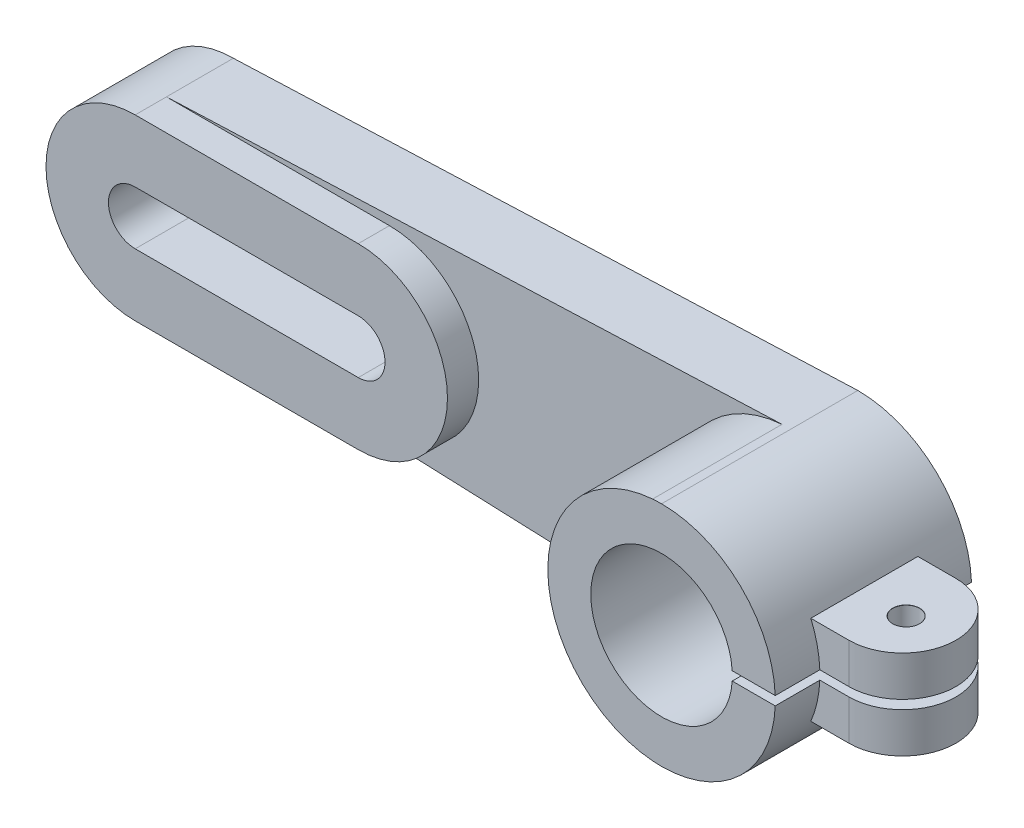
SolidWorks part; units mm, degrees
ref_plane "Front Plane" through (0, 0, 0) normal (0, 0, 1) x (1, 0, 0)
ref_plane "Top Plane" through (0, 0, 0) normal (0, 1, 0) x (1, 0, 0)
ref_plane "Right Plane" through (0, 0, 0) normal (1, 0, 0) x (0, 0, -1)
sketch "Sketch1" plane through (0, 0, 0) normal (0, 0, 1) x (1, 0, 0)
  line L0 (0, 0) -> (0, -27672.145) construction
  line L1 (0, 0) -> (-27672.145, 0) construction
  line L2 (-90, 0) -> (-140, 0) construction
  line L3 (-90, -6) -> (-140, -6)
  line L4 (-90, 6) -> (-140, 6)
  line L5 (-140, 0) -> (-90, 0) construction
  line L6 (-140, 20) -> (-90, 20)
  line L7 (-140, -20) -> (-90, -20)
  line L8 (0, 25.5) -> (-140, 20)
  line L9 (0, -25.5) -> (-140, -20)
  line L10 (15.836, 1) -> (44, 1)
  line L11 (44, 1) -> (44, 10)
  line L12 (44, 10) -> (23.4574, 10)
  line L13 (44, -1) -> (44, -10)
  line L14 (15.836, -1) -> (44, -1)
  line L15 (44, -10) -> (23.4574, -10)
  circle A0 centre (0, 0) radius 25.5
  arc A1 (15.836, 1) -> (15.836, -1) centre (0, 0) ccw
  arc A2 (-90, -6) -> (-90, 6) centre (-90, 0) ccw
  arc A3 (-140, 6) -> (-140, -6) centre (-140, 0) ccw
  arc A4 (-140, 20) -> (-140, -20) centre (-140, 0) ccw
  arc A5 (-90, -20) -> (-90, 20) centre (-90, 0) ccw
  point P10 (-115, 0)
  point P15 (-115, 0)
  point P28 (0, 0)
  dimension "D1" = 51
  dimension "D2" = 31.735
  dimension "D4" = 20
  dimension "D7" = 9
  dimension "D3" = 12
  dimension "D5" = 50
  dimension "D6" = 140
  dimension "D8" = 44
  dimension "D9" = 20
extrude "Boss-Extrude1" add sketch "Sketch1" along normal blind 44 contours A1 L10 A0 L8 L9 L14 region at (-0.9719, 24.7402, 0)
extrude "Boss-Extrude2" add sketch "Sketch1<3>" along normal blind 15 contours A5 L7 L9 A0 L8 L6 region at (-49.8705, 0, 0)
sketch "Sketch1<3>" plane through (0, 0, 0) normal (0, 0, 1) x (1, 0, 0) same geometry as "Sketch1"
extrude "Boss-Extrude3" add sketch "Sketch1<4>" along normal blind 22 contours L7 A5 L6 A4 A3 L4 A2 L3 region at (-115, 19.0151, 0)
sketch "Sketch1<4>" plane through (0, 0, 0) normal (0, 0, 1) x (1, 0, 0) same geometry as "Sketch1"
extrude "Boss-Extrude4" add sketch "Sketch1<5>" along normal blind 24 from offset 10 contours A0 L10 L11 L12 | A0 L15 L13 L14 region at (34.3692, 5.5783, 0) region at (34.3692, -5.5783, 0)
sketch "Sketch1<5>" plane through (0, 0, 0) normal (0, 0, 1) x (1, 0, 0) same geometry as "Sketch1"
fillet "Fillet1" 2 edges at (44, 5.5, 34) (44, 5.5, 10) type full round first side face at (34.337, 5.5231, 34) second side face at (34.337, 5.5231, 10) middle face at (44, 5.5, 22)
fillet "Fillet2" 2 edges at (44, -5.5, 34) (44, -5.5, 10) type full round first side face at (34.337, -5.5231, 34) second side face at (34.337, -5.5231, 10) middle face at (44, -5.5, 22)
hole_wizard "Ø6.0mm Dowel Hole1" positions "Sketch4" profile "Sketch5" hole size "Ø6.0" standard "ISO" end condition through all
sketch "Sketch4" plane through (0, 10, 0) normal (0, 1, 0) x (1, 0, 0)
  point P0 (33.6932, -22.8639)
sketch "Sketch5" plane through (33.6932, 10, 22.8639) normal (1, 0, 0) x (0, 0, 1)
  line L0 (0, 0) -> (0, 35.5)
  line L1 (0, 35.5) -> (3, 35.5)
  line L2 (3, 35.5) -> (3, 0.025)
  line L3 (3, 0.025) -> (3.025, 0)
  line L5 (3.025, 0) -> (0, 0)
  line L6 (-3, 0.025) -> (-3.025, 0) construction
  line L11 (0, -6.35) -> (0, 107.95) construction
  dimension "Thru Hole Dia." = 6
  dimension "Thru Hole Depth" = 35.5
  dimension "Near C'Sink Dia." = 6.05
  dimension "Near C'Sink Angle" = 90
